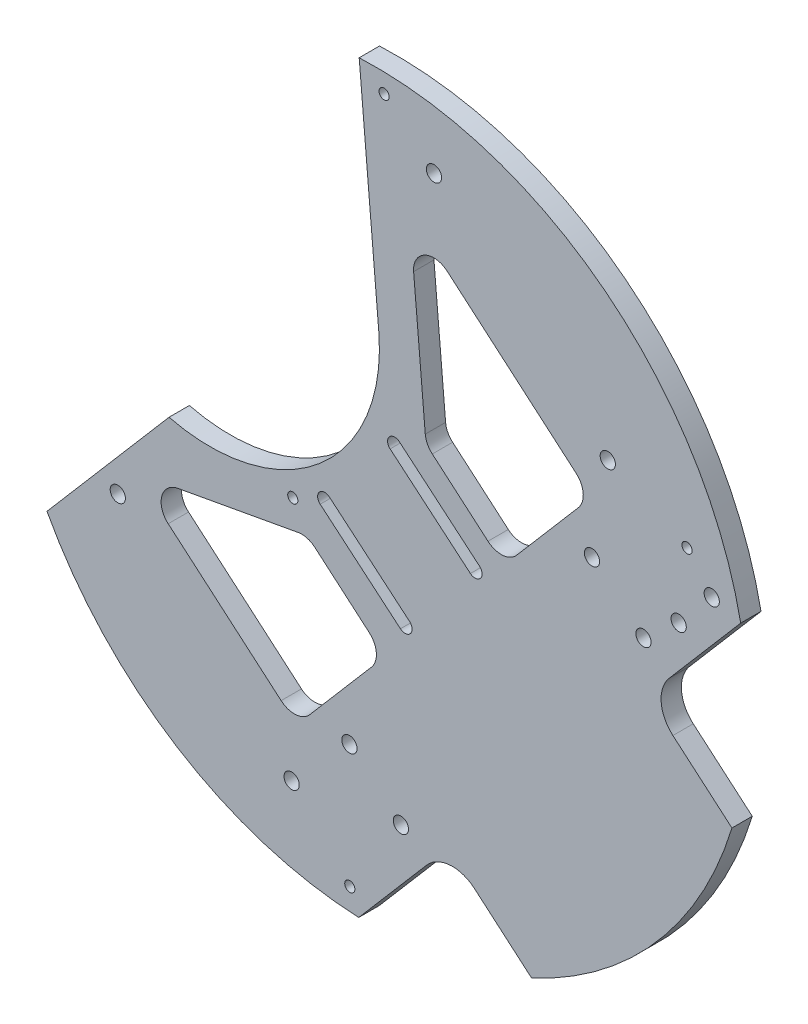
SolidWorks part; units mm, degrees
material "PMMA"
ref_plane "Front Plane" through (0, 0, 0) normal (0, 0, 1) x (1, 0, 0)
ref_plane "Top Plane" through (0, 0, 0) normal (0, 1, 0) x (1, 0, 0)
ref_plane "Right Plane" through (0, 0, 0) normal (1, 0, 0) x (0, 0, -1)
sketch "Sketch1" plane through (0, 0, 0) normal (0, 0, 1) x (1, 0, 0)
  line L0 (-65.0357, 1.7119) -> (-29.0137, 43.7635)
  line L1 (27.0989, 163.6983) -> (32.8912, 96.5787)
  arc A5 (-65.0357, 1.7119) -> (27.0989, 163.6983) centre (31.8495, 53.8009) ccw
  arc A6 (-29.0137, 43.7635) -> (32.8912, 96.5787) centre (-16.9236, 92.2798) ccw
  circle A7 centre (-44.1307, 16.5884) radius 2.25
  circle A8 centre (7.1608, -31.0475) radius 2.25
  circle A9 centre (100.4703, 97.5518) radius 2.25
  circle A10 centre (49.1788, 145.1877) radius 2.25
  dimension "D1" = 220
  dimension "D2" = 100
  dimension "D6" = 4.5
  dimension "D3" = 60.8633
  dimension "D4" = 55.3707
  dimension "D5" = 67.1195
extrude "Boss-Extrude1" add sketch "Sketch1" along normal blind 6
sketch "Sketch2" plane through (0, 0, 6) normal (0, 0, 1) x (1, 0, 0)
  line L0 (61.2734, 49.8977) -> (37.5872, 69.8968) construction
  line L1 (59.9186, 48.2932) -> (36.2324, 68.2923)
  line L2 (62.6282, 51.5023) -> (38.942, 71.5014)
  line L3 (40.6292, 25.4474) -> (16.943, 45.4465) construction
  line L4 (39.2744, 23.8429) -> (15.5882, 43.842)
  line L5 (41.984, 27.052) -> (18.2978, 47.0511)
  line L6 (61.2734, 49.8977) -> (46.5625, 32.4747) construction
  line L7 (46.5625, 32.4747) -> (37.9334, 22.2547) construction
  line L8 (15.0411, 41.8646) -> (37.8247, 22.3478) construction
  line L9 (50.2278, 38.2835) -> (29.8022, 55.5295) construction
  line L11 (16.943, 45.4465) -> (37.5872, 69.8968) construction
  arc A0 (59.9186, 48.2932) -> (62.6282, 51.5023) centre (61.2734, 49.8977) ccw
  arc A1 (38.942, 71.5014) -> (36.2324, 68.2923) centre (37.5872, 69.8968) ccw
  arc A2 (39.2744, 23.8429) -> (41.984, 27.052) centre (40.6292, 25.4474) ccw
  arc A3 (18.2978, 47.0511) -> (15.5882, 43.842) centre (16.943, 45.4465) ccw
  circle A5 centre (58.207, 52.2904) radius 2.25 construction
  point P4 (49.4303, 59.8973)
  point P9 (28.7861, 35.447)
  dimension "D1" = 4.2
  dimension "D2" = 4.2
  dimension "D3" = 25
  dimension "D4" = 16
  dimension "D5" = 32
  dimension "D6" = 31
  dimension "D7" = 31
  dimension "D8" = 16
extrude "Cut-Extrude1" cut sketch "Sketch2" against normal blind 10
hole_wizard "Ø4.5 (4.5) Diameter Hole" positions "Sketch3" profile "Sketch4" hole size "Ø4.5" standard "IS"
sketch "Sketch3" plane through (207.2158, -96.42, 6) normal (0, 0, 1) x (-0.6506, -0.7595, 0)
  point P0 (80.5001, -194.4616)
  point P3 (77.6909, -264.4052)
  point P6 (-80.6779, -277.2022)
  point P9 (-77.8687, -207.2586)
sketch "Sketch4" plane through (7.1608, -31.0475, 6) normal (1, 0, 0) x (0, -1, 0)
  line L0 (0, 0) -> (0, 11.3519)
  line L1 (0, 11.3519) -> (2.25, 10)
  line L2 (2.25, 10) -> (2.25, 0)
  line L3 (2.25, 0) -> (0, 0)
  line L4 (0, 11.3519) -> (-2.25, 10) construction
  line L5 (0, -6.35) -> (0, 107.95) construction
  dimension "Hole Dia." = 4.5
  dimension "Hole Depth" = 10
  dimension "Drill Angle" = 118
hole_wizard "Ø3.0mm Dowel Hole1" positions "Sketch5" profile "Sketch6" hole size "Ø3.0" standard "IS" end condition through all
sketch "Sketch5" plane through (207.2158, -96.42, 6) normal (0, 0, 1) x (-0.6506, -0.7595, 0)
  point P0 (-80.9158, -296.795)
  point P3 (-84.9452, -182.5189)
  point P6 (25.2163, -241.3641)
  point P9 (83.3286, -169.4245)
sketch "Sketch6" plane through (34.4537, 158.1146, 6) normal (1, 0, 0) x (0, -1, 0)
  line L0 (0, 0) -> (0, 6)
  line L1 (0, 6) -> (1.5, 6)
  line L2 (1.5, 6) -> (1.5, 0)
  line L3 (1.5, 0) -> (0, 0)
  line L4 (0, -6.35) -> (0, 107.95) construction
  dimension "Thru Hole Dia." = 3
  dimension "Thru Hole Depth" = 6
sketch "Sketch7" plane through (0, 0, 6) normal (0, 0, 1) x (1, 0, 0)
  line L0 (139.6892, 75.4943) -> (26.9717, -56.0909) construction
  line L1 (43.1676, 117.0689) -> (46.6032, 77.2574)
  line L2 (37.8247, 22.3478) -> (46.282, 32.2207) construction
  line L3 (139.6892, 75.4943) -> (118.5944, 50.8684)
  line L4 (119.6834, 36.7683) -> (137.1053, 21.8444)
  line L5 (84.7002, 70.5146) -> (146.9827, 12.671) construction
  line L6 (137.1053, 21.8444) -> (157.1792, 45.2784)
  line L7 (157.1792, 45.2784) -> (139.6892, 75.4943)
  line L8 (26.9717, -56.0909) -> (47.0048, -32.7045)
  line L9 (61.105, -31.6155) -> (77.9709, -46.0631)
  line L10 (23.454, 4.5684) -> (85.7366, -53.2753) construction
  line L11 (77.9709, -46.0631) -> (19.4206, -114.4141)
  line L12 (19.4206, -114.4141) -> (26.9717, -56.0909)
  line L13 (39.4103, -26.1989) -> (110.9998, 57.374) construction
  line L14 (110.9998, 57.374) -> (95.8107, 70.3852) construction
  line L15 (95.8107, 70.3852) -> (24.2212, -13.1877) construction
  line L16 (24.2212, -13.1877) -> (39.4103, -26.1989) construction
  line L17 (121.3842, 66.4224) -> (131.1426, 77.8142) construction
  line L22 (48.6776, 73.2165) -> (65.1103, 59.1401)
  line L23 (73.5704, 59.7935) -> (91.786, 81.0582)
  line L24 (91.1326, 89.5183) -> (53.0487, 122.1415)
  line L26 (27.0989, 163.6983) -> (32.8912, 96.5787) construction
  line L28 (97.3288, 86.8219) -> (87.8033, 95.6685) construction
  line L29 (30.0871, 18.2544) -> (14.0299, 32.0092)
  line L30 (9.0496, 33.355) -> (-26.4328, 26.8812)
  line L31 (-29.2593, 16.422) -> (4.0648, -12.1238)
  line L32 (12.5249, -11.4704) -> (30.7405, 9.7943)
  line L33 (17.6296, -27.1227) -> (8.104, -18.2761) construction
  line L35 (-29.0137, 43.7635) -> (-65.0357, 1.7119) construction
  arc A0 (-65.0357, 1.7119) -> (27.0989, 163.6983) centre (31.8495, 53.8009) ccw construction
  arc A1 (65.1103, 59.1401) -> (73.5704, 59.7935) centre (69.0136, 63.6968) ccw
  circle A2 centre (34.4537, 158.1146) radius 1.6 construction
  arc A3 (118.5944, 50.8684) -> (119.6834, 36.7683) centre (126.1889, 44.3629) ccw
  arc A4 (47.0048, -32.7045) -> (61.105, -31.6155) centre (54.5994, -39.2101) cw
  circle A5 centre (39.4103, -26.1989) radius 2.25
  circle A6 centre (110.9998, 57.374) radius 2.25
  circle A7 centre (24.2212, -13.1877) radius 2.25
  circle A8 centre (95.8107, 70.3852) radius 2.25
  circle A9 centre (121.3842, 66.4224) radius 2.25
  circle A10 centre (131.1426, 77.8142) radius 2.25
  arc A11 (46.6032, 77.2574) -> (48.6776, 73.2165) centre (52.581, 77.7732) ccw
  arc A12 (43.1676, 117.0689) -> (53.0487, 122.1415) centre (49.1453, 117.5848) cw
  arc A13 (91.786, 81.0582) -> (91.1326, 89.5183) centre (87.2293, 84.9616) ccw
  arc A14 (14.0299, 32.0092) -> (9.0496, 33.355) centre (10.1266, 27.4525) ccw
  arc A15 (30.0871, 18.2544) -> (30.7405, 9.7943) centre (26.1838, 13.6977) cw
  arc A16 (4.0648, -12.1238) -> (12.5249, -11.4704) centre (7.9681, -7.5671) ccw
  arc A17 (-26.4328, 26.8812) -> (-29.2593, 16.422) centre (-25.3559, 20.9787) ccw
  point P22 (112.0888, 43.2739)
  point P25 (53.5104, -25.1099)
  point P55 (69.667, 55.2367)
  point P62 (95.6894, 85.615)
  point P65 (11.8602, 33.8678)
  point P68 (34.6439, 14.3511)
  point P71 (8.6215, -16.0272)
  point P74 (-38.8291, 24.6195)
  dimension "D8" = 10
  dimension "D9" = 4.5
  dimension "D26" = 6
  dimension "D1" = 214.3362
  dimension "D2" = 90
  dimension "D3" = 90
  dimension "D4" = 90
  dimension "D5" = 30.8563
  dimension "D6" = 90
  dimension "D7" = 90
  dimension "D10" = 20
  dimension "D11" = 10
  dimension "D12" = 10
  dimension "D13" = 10
  dimension "D14" = 8
  dimension "D15" = 15
  dimension "D16" = 15.5539
  dimension "D17" = 12
  dimension "D18" = 2
  dimension "D19" = 40
  dimension "D20" = 40
  dimension "D21" = 40
  dimension "D22" = 2
  dimension "D23" = 40
  dimension "D24" = 5
  dimension "D25" = 30
extrude "Cut-Extrude2" cut sketch "Sketch7" against normal blind 10
